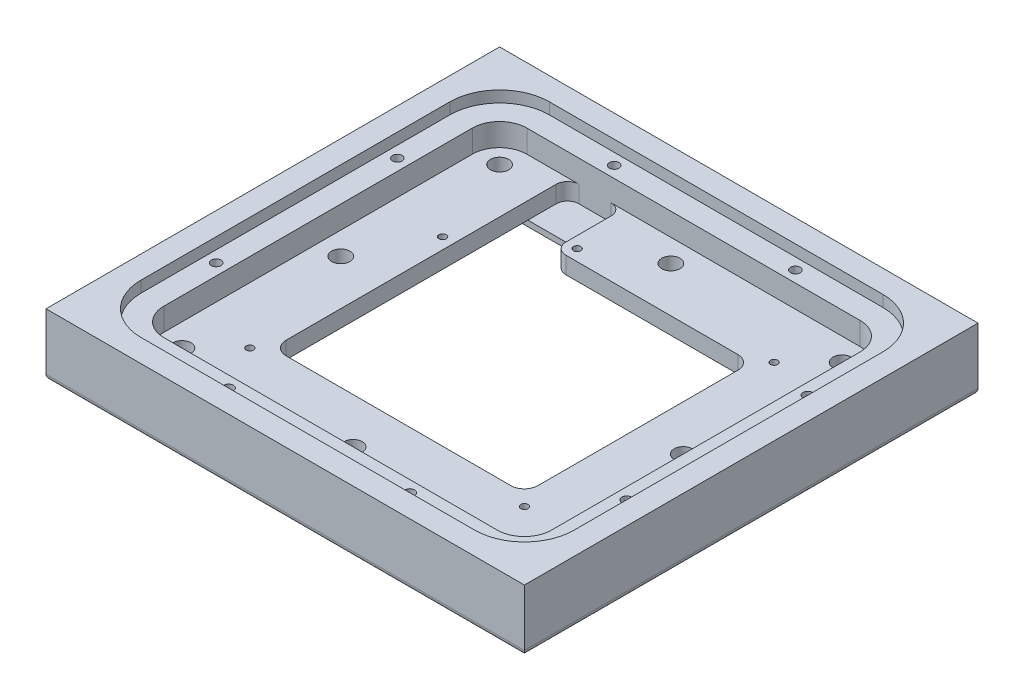
SolidWorks part; units mm, degrees
material "PE High Density"
ref_plane "Front Plane" through (0, 0, 0) normal (0, 0, 1) x (1, 0, 0)
ref_plane "Top Plane" through (0, 0, 0) normal (0, 1, 0) x (1, 0, 0)
ref_plane "Right Plane" through (0, 0, 0) normal (1, 0, 0) x (0, 0, -1)
sketch "Sketch2" plane through (0, 0, 0) normal (0, 1, 0) x (1, 0, 0)
  line L0 (-41.656, 22.1996) -> (-19.9136, 22.1996)
  line L1 (41.656, -38.1762) -> (-41.656, -38.1762)
  line L2 (41.656, -38.1762) -> (41.656, 38.1762)
  line L3 (41.656, 38.1762) -> (-41.656, 38.1762)
  line L4 (-41.656, -38.1762) -> (-41.656, 38.1762)
  line L5 (41.656, -38.1762) -> (-41.656, 38.1762) construction
  line L6 (41.656, 38.1762) -> (-41.656, -38.1762) construction
  line L7 (-19.9136, 22.1996) -> (-19.9136, 38.1762)
  line L8 (67.056, -63.5762) -> (-67.056, -63.5762)
  line L9 (-67.056, -63.5762) -> (-67.056, 63.5762)
  line L10 (67.056, 63.5762) -> (-67.056, 63.5762)
  line L11 (67.056, -63.5762) -> (67.056, 63.5762)
  point P0 (0, 0)
  point P13 (-38.481, -35.0012)
  point P14 (38.481, -35.0012)
  point P15 (38.481, 35.0012)
  point P16 (-16.7386, 35.0012)
  point P17 (-38.481, 19.0246)
  dimension "D1" = 83.312
  dimension "D2" = 76.3524
  dimension "D3" = 21.7424
  dimension "D4" = 15.9766
  dimension "D6" = 3.175
  dimension "D7" = 3.175
  dimension "D8" = 57.2008
  dimension "D9" = 80.137
  dimension "D10" = 24.9174
  dimension "D11" = 73.1774
  dimension "D5" = 25.4
extrude "Boss-Extrude1" add sketch "Sketch2" along normal blind 15.875 contours L8 L11 L10 L9 L1 L4 L3 L2 | L0 L7 L3 L4 region at (-30.7848, 0, -30.1879) region at (0, 0, 61.7281)
sketch "Sketch4" plane through (0, 0, 0) normal (0, 1, 0) x (1, 0, 0)
  line L0 (41.656, -38.1762) -> (41.656, 38.1762) construction
  line L1 (41.656, 38.1762) -> (-19.9136, 38.1762) construction
  line L2 (41.656, -38.1762) -> (-41.656, -38.1762) construction
  line L3 (-41.656, -38.1762) -> (-41.656, 22.1996) construction
  line L4 (-41.656, 22.1996) -> (-19.9136, 22.1996) construction
  line L5 (41.656, -38.1762) -> (41.656, 38.1762)
  line L6 (41.656, 38.1762) -> (-19.9136, 38.1762)
  line L7 (41.656, -38.1762) -> (-41.656, -38.1762)
  line L8 (-41.656, -38.1762) -> (-41.656, 22.1996)
  line L9 (-41.656, 22.1996) -> (-19.9136, 22.1996)
  line L10 (-19.9136, 22.1996) -> (-19.9136, 38.1762) construction
  line L11 (-19.9136, 22.1996) -> (-19.9136, 38.1762)
  line L12 (35.306, 31.8262) -> (-13.5636, 31.8262)
  line L13 (-13.5636, 15.8496) -> (-13.5636, 31.8262)
  line L14 (-35.306, 15.8496) -> (-13.5636, 15.8496)
  line L15 (-35.306, -31.8262) -> (-35.306, 15.8496)
  line L16 (35.306, -31.8262) -> (-35.306, -31.8262)
  line L17 (35.306, -31.8262) -> (35.306, 31.8262)
  dimension "D1" = 6.35
extrude "Boss-Extrude2" add sketch "Sketch4" along normal blind 9.525
sketch "Sketch5" plane through (0, 0, 0) normal (0, -1, 0) x (1, 0, 0)
  line L5 (46.736, -50.8762) -> (-46.736, -50.8762)
  line L6 (54.356, -43.2562) -> (54.356, 43.2562)
  line L7 (46.736, 50.8762) -> (-46.736, 50.8762)
  line L8 (-54.356, -43.2562) -> (-54.356, 43.2562)
  line L9 (54.356, -50.8762) -> (-54.356, 50.8762) construction
  line L10 (54.356, 50.8762) -> (-54.356, -50.8762) construction
  arc A0 (46.736, -50.8762) -> (54.356, -43.2562) centre (46.736, -43.2562) ccw
  arc A1 (-46.736, -50.8762) -> (-54.356, -43.2562) centre (-46.736, -43.2562) cw
  arc A2 (54.356, 43.2562) -> (46.736, 50.8762) centre (46.736, 43.2562) ccw
  arc A3 (-46.736, 50.8762) -> (-54.356, 43.2562) centre (-46.736, 43.2562) ccw
  point P0 (0, 0)
  dimension "D3" = 7.62
  dimension "D1" = 108.712
  dimension "D2" = 101.7524
extrude "Cut-Extrude2" cut sketch "Sketch5" against normal blind 3.175
hole_wizard "M2.5x0.45 Tapped Hole1" positions "Sketch6" profile "Sketch7" tap size "M2.5x0.45" standard "ANSI Metric"
sketch "Sketch6" plane through (0, 3.175, 0) normal (0, -1, 0) x (-1, 0, 0)
  point P0 (38.481, -35.0012)
  point P3 (-38.481, -35.0012)
  point P6 (38.481, 19.0246)
  point P9 (16.7386, 35.0012)
  point P12 (-38.481, 35.0012)
sketch "Sketch7" plane through (-38.481, 3.175, 35.0012) normal (1, 0, 0) x (0, 0, -1)
  line L0 (0, 0) -> (0, 6.9659)
  line L1 (0, 6.9659) -> (1.025, 6.35)
  line L2 (1.025, 6.35) -> (1.025, 0)
  line L5 (1.025, 0) -> (0, 0)
  line L10 (0, 6.9659) -> (-1.025, 6.35) construction
  line L11 (0, -6.35) -> (0, 107.95) construction
  dimension "Tap Drill Dia." = 2.05
  dimension "Tap Drill Depth" = 6.35
  dimension "Drill Angle" = 118
cosmetic thread "Hole Thread1" parameters "D1"=5.08, "D2"=2.5
cosmetic thread "Hole Thread2" parameters "D1"=5.08, "D2"=2.5
cosmetic thread "Hole Thread3" parameters "D1"=5.08, "D2"=2.5
cosmetic thread "Hole Thread4" parameters "D1"=5.08, "D2"=2.5
cosmetic thread "Hole Thread5" parameters "D1"=5.08, "D2"=2.5
hole_wizard "#10 Clearance Hole1" positions "Sketch8" profile "Sketch9" hole size "#10" standard "ANSI Inch" end condition through all
sketch "Sketch8" plane through (0, 3.175, 0) normal (0, -1, 0) x (-1, 0, 0)
  line L0 (54.356, -43.2562) -> (54.356, 43.2562) construction
  line L1 (-46.736, -50.8762) -> (46.736, -50.8762) construction
  line L2 (46.736, 50.8762) -> (-46.736, 50.8762) construction
  line L3 (-54.356, 43.2562) -> (-54.356, -43.2562) construction
  point P0 (48.006, -44.5262)
  point P2 (0, -44.5262)
  point P4 (-48.006, -44.5262)
  point P6 (-48.006, 0)
  point P8 (-48.006, 44.5262)
  point P10 (0, 44.5262)
  point P12 (48.006, 44.5262)
  point P14 (48.006, 0)
  dimension "D1" = 6.35
  dimension "D2" = 6.35
  dimension "D3" = 6.35
  dimension "D4" = 6.35
sketch "Sketch9" plane through (-48.006, 3.175, 44.5262) normal (1, 0, 0) x (0, 0, -1)
  line L0 (0, 0) -> (0, 12.7)
  line L1 (0, 12.7) -> (2.5527, 12.7)
  line L2 (2.5527, 12.7) -> (2.5527, 0)
  line L5 (2.5527, 0) -> (0, 0)
  line L11 (0, -6.35) -> (0, 107.95) construction
  dimension "Thru Hole Dia." = 5.1054
  dimension "Thru Hole Depth" = 12.7
sketch "Sketch10" plane through (0, 15.875, 0) normal (0, 1, 0) x (1, 0, 0)
  line L4 (54.356, -43.2562) -> (54.356, 43.2562)
  line L5 (-46.736, -50.8762) -> (46.736, -50.8762)
  line L6 (-54.356, 43.2562) -> (-54.356, -43.2562)
  line L7 (46.736, 50.8762) -> (-46.736, 50.8762)
  line L8 (54.356, -43.2562) -> (54.356, 43.2562)
  line L9 (-46.736, -50.8762) -> (46.736, -50.8762)
  line L10 (-54.356, 43.2562) -> (-54.356, -43.2562)
  line L11 (46.736, 50.8762) -> (-46.736, 50.8762)
  arc A4 (54.356, 43.2562) -> (46.736, 50.8762) centre (46.736, 43.2562) ccw
  arc A5 (46.736, -50.8762) -> (54.356, -43.2562) centre (46.736, -43.2562) ccw
  arc A6 (-54.356, -43.2562) -> (-46.736, -50.8762) centre (-46.736, -43.2562) ccw
  arc A7 (-46.736, 50.8762) -> (-54.356, 43.2562) centre (-46.736, 43.2562) ccw
  arc A8 (54.356, 43.2562) -> (46.736, 50.8762) centre (46.736, 43.2562) ccw
  arc A9 (46.736, -50.8762) -> (54.356, -43.2562) centre (46.736, -43.2562) ccw
  arc A10 (-54.356, -43.2562) -> (-46.736, -50.8762) centre (-46.736, -43.2562) ccw
  arc A11 (-46.736, 50.8762) -> (-54.356, 43.2562) centre (-46.736, 43.2562) ccw
  dimension "D1" = 0
extrude "Cut-Extrude3" cut sketch "Sketch10" against normal up to surface (6.35 mm away) up to face at (-38.481, 9.525, 33.9762)
sketch "Sketch11" plane through (0, 3.175, 0) normal (0, -1, 0) x (1, 0, 0)
  line L8 (43.2435, 39.7637) -> (-43.2435, 39.7637)
  line L9 (-43.2435, 39.7637) -> (-43.2435, -39.7637)
  line L10 (-43.2435, -39.7637) -> (43.2435, -39.7637)
  line L11 (43.2435, -39.7637) -> (43.2435, 39.7637)
  line L12 (40.0685, 39.7637) -> (-40.0685, 39.7637)
  line L13 (-43.2435, 36.5887) -> (-43.2435, -36.5887)
  line L14 (-40.0685, -39.7637) -> (40.0685, -39.7637)
  line L15 (43.2435, -36.5887) -> (43.2435, 36.5887)
  arc A0 (40.0685, -39.7637) -> (43.2435, -36.5887) centre (40.0685, -36.5887) ccw
  arc A1 (-43.2435, -36.5887) -> (-40.0685, -39.7637) centre (-40.0685, -36.5887) ccw
  arc A2 (40.0685, 39.7637) -> (43.2435, 36.5887) centre (40.0685, 36.5887) cw
  arc A3 (-40.0685, 39.7637) -> (-43.2435, 36.5887) centre (-40.0685, 36.5887) ccw
  dimension "D2" = 3.175
  dimension "D1" = 1.5875
extrude "Cut-Extrude4" cut sketch "Sketch11" against normal blind 1.6
sketch "Sketch12" plane through (0, 4.775, 0) normal (0, -1, 0) x (1, 0, 0)
  line L0 (-35.306, 31.8262) -> (-35.306, -15.8496) construction
  line L1 (35.306, 31.8262) -> (-35.306, 31.8262)
  line L2 (35.306, 31.8262) -> (35.306, -31.8262)
  line L3 (35.306, -31.8262) -> (-35.306, -31.8262)
  line L4 (-35.306, 31.8262) -> (-35.306, -31.8262)
  line L5 (-13.5636, -31.8262) -> (35.306, -31.8262) construction
extrude "Cut-Extrude5" cut sketch "Sketch12" against normal through all
fillet "Fillet1" radius 3.81 4 edges at (35.306, 7.15, -31.8262) (-35.306, 7.15, -31.8262) (35.306, 7.15, 31.8262) (-35.306, 7.15, 31.8262)
sketch "Sketch13" plane through (0, 0, 0) normal (0, -1, 0) x (1, 0, 0)
  line L4 (54.356, -43.2562) -> (54.356, 43.2562)
  line L5 (46.736, 50.8762) -> (-46.736, 50.8762)
  line L6 (-54.356, 43.2562) -> (-54.356, -43.2562)
  line L7 (-46.736, -50.8762) -> (46.736, -50.8762)
  line L8 (54.356, -43.2562) -> (54.356, 43.2562)
  line L9 (46.736, 50.8762) -> (-46.736, 50.8762)
  line L10 (-54.356, 43.2562) -> (-54.356, -43.2562)
  line L11 (-46.736, -50.8762) -> (46.736, -50.8762)
  line L12 (67.056, 63.5762) -> (-67.056, 63.5762)
  line L13 (-67.056, 63.5762) -> (-67.056, -63.5762)
  line L14 (-67.056, -63.5762) -> (67.056, -63.5762)
  line L15 (67.056, -63.5762) -> (67.056, 63.5762)
  line L16 (67.056, 63.5762) -> (-67.056, 63.5762)
  line L17 (-67.056, 63.5762) -> (-67.056, -63.5762)
  line L18 (-67.056, -63.5762) -> (67.056, -63.5762)
  line L19 (67.056, -63.5762) -> (67.056, 63.5762)
  arc A4 (46.736, -50.8762) -> (54.356, -43.2562) centre (46.736, -43.2562) ccw
  arc A5 (54.356, 43.2562) -> (46.736, 50.8762) centre (46.736, 43.2562) ccw
  arc A6 (-46.736, 50.8762) -> (-54.356, 43.2562) centre (-46.736, 43.2562) ccw
  arc A7 (-54.356, -43.2562) -> (-46.736, -50.8762) centre (-46.736, -43.2562) ccw
  arc A8 (46.736, -50.8762) -> (54.356, -43.2562) centre (46.736, -43.2562) ccw
  arc A9 (54.356, 43.2562) -> (46.736, 50.8762) centre (46.736, 43.2562) ccw
  arc A10 (-46.736, 50.8762) -> (-54.356, 43.2562) centre (-46.736, 43.2562) ccw
  arc A11 (-54.356, -43.2562) -> (-46.736, -50.8762) centre (-46.736, -43.2562) ccw
  dimension "D1" = 0
  dimension "D2" = 0
extrude "Cut-Extrude6" cut sketch "Sketch13" against normal blind 1.5875
fillet "Fillet2" radius 1.5875 4 edges at (67.056, 1.5875, 0) (0, 1.5875, 63.5762) (-67.056, 1.5875, 0) (0, 1.5875, -63.5762)
sketch "Sketch14" plane through (0, 9.525, 0) normal (0, 1, 0) x (1, 0, 0)
  line L1 (-35.306, 28.0162) -> (-19.9136, 28.0162)
  line L2 (-35.306, 28.0162) -> (-35.306, 50.8762)
  line L3 (-35.306, 50.8762) -> (-19.9136, 50.8762)
  line L4 (-19.9136, 28.0162) -> (-19.9136, 50.8762)
  line L6 (46.736, 50.8762) -> (-46.736, 50.8762) construction
  circle A0 centre (-16.7386, 35.0012) radius 1.025 construction
  dimension "D1" = 3.175
extrude "Cut-Extrude7" cut sketch "Sketch14" against normal up to surface (4.75 mm away) up to face at (0, 4.775, 0)
fillet "Fillet3" radius 3.175 3 edges at (-19.9136, 7.15, -50.8762) (-35.306, 7.15, -50.8762) (-19.9136, 7.15, -31.8262)
sketch "Sketch15" plane through (0, 15.875, 0) normal (0, 1, 0) x (1, 0, 0)
  line L0 (54.356, -43.2562) -> (54.356, 43.2562) construction
  line L1 (-46.736, -50.8762) -> (46.736, -50.8762) construction
  line L2 (-54.356, 43.2562) -> (-54.356, -43.2562) construction
  line L3 (46.736, 50.8762) -> (-46.736, 50.8762) construction
  line L4 (54.356, -43.2562) -> (54.356, 43.2562)
  line L5 (-46.736, -50.8762) -> (46.736, -50.8762)
  line L6 (-54.356, 43.2562) -> (-54.356, -43.2562)
  line L7 (46.736, 50.8762) -> (-46.736, 50.8762)
  line L8 (60.706, -43.2562) -> (60.706, 43.2562)
  line L9 (46.736, 57.2262) -> (-46.736, 57.2262)
  line L10 (-60.706, 43.2562) -> (-60.706, -43.2562)
  line L11 (-46.736, -57.2262) -> (46.736, -57.2262)
  line L16 (-67.056, -63.5762) -> (67.056, -63.5762)
  line L17 (67.056, -63.5762) -> (67.056, 63.5762)
  line L18 (67.056, 63.5762) -> (-67.056, 63.5762)
  line L19 (-67.056, 63.5762) -> (-67.056, -63.5762)
  line L20 (-67.056, -63.5762) -> (67.056, -63.5762)
  line L21 (67.056, -63.5762) -> (67.056, 63.5762)
  line L22 (67.056, 63.5762) -> (-67.056, 63.5762)
  line L23 (-67.056, 63.5762) -> (-67.056, -63.5762)
  arc A0 (46.736, -50.8762) -> (54.356, -43.2562) centre (46.736, -43.2562) ccw construction
  arc A1 (-54.356, -43.2562) -> (-46.736, -50.8762) centre (-46.736, -43.2562) ccw construction
  arc A2 (54.356, 43.2562) -> (46.736, 50.8762) centre (46.736, 43.2562) ccw construction
  arc A3 (-46.736, 50.8762) -> (-54.356, 43.2562) centre (-46.736, 43.2562) ccw construction
  arc A4 (46.736, -50.8762) -> (54.356, -43.2562) centre (46.736, -43.2562) ccw
  arc A5 (-54.356, -43.2562) -> (-46.736, -50.8762) centre (-46.736, -43.2562) ccw
  arc A6 (54.356, 43.2562) -> (46.736, 50.8762) centre (46.736, 43.2562) ccw
  arc A7 (-46.736, 50.8762) -> (-54.356, 43.2562) centre (-46.736, 43.2562) ccw
  arc A8 (60.706, 43.2562) -> (46.736, 57.2262) centre (46.736, 43.2562) ccw
  arc A9 (-46.736, 57.2262) -> (-60.706, 43.2562) centre (-46.736, 43.2562) ccw
  arc A10 (-60.706, -43.2562) -> (-46.736, -57.2262) centre (-46.736, -43.2562) ccw
  arc A11 (46.736, -57.2262) -> (60.706, -43.2562) centre (46.736, -43.2562) ccw
  line M29 (-67.056, -63.5762) -> (67.056, -63.5762)
  line M30 (67.056, -63.5762) -> (67.056, 63.5762)
  line M31 (67.056, 63.5762) -> (-67.056, 63.5762)
  line M32 (-67.056, 63.5762) -> (-67.056, -63.5762)
  dimension "D1" = 6.35
  dimension "D2" = 0
extrude "Boss-Extrude3" add sketch "Sketch15" along normal blind 3.175 contours A11 L11 A10 L10 A9 L9 A8 L8 M32 M29 M30 M31 region at (-65.2079, 15.875, 0)
hole_wizard "#6-32 Tapped Hole1" positions "Sketch16" profile "Sketch18" tap size "#6-32" standard "ANSI Inch"
sketch "Sketch16" plane through (0, 15.875, 0) normal (0, 1, 0) x (1, 0, 0)
  line L28 (57.531, -43.2562) -> (57.531, 43.2562)
  line L29 (-46.736, -54.0512) -> (46.736, -54.0512)
  line L30 (-57.531, 43.2562) -> (-57.531, -43.2562)
  line L31 (46.736, 54.0512) -> (-46.736, 54.0512)
  line L32 (57.531, -43.2562) -> (57.531, 43.2562) construction
  line L33 (-46.736, -54.0512) -> (46.736, -54.0512) construction
  line L34 (-57.531, 43.2562) -> (-57.531, -43.2562) construction
  line L35 (46.736, 54.0512) -> (-46.736, 54.0512) construction
  arc A24 (57.531, 43.2562) -> (46.736, 54.0512) centre (46.736, 43.2562) ccw
  arc A25 (46.736, -54.0512) -> (57.531, -43.2562) centre (46.736, -43.2562) ccw
  arc A26 (-57.531, -43.2562) -> (-46.736, -54.0512) centre (-46.736, -43.2562) ccw
  arc A27 (-46.736, 54.0512) -> (-57.531, 43.2562) centre (-46.736, 43.2562) ccw
  arc A28 (57.531, 43.2562) -> (46.736, 54.0512) centre (46.736, 43.2562) ccw construction
  arc A29 (46.736, -54.0512) -> (57.531, -43.2562) centre (46.736, -43.2562) ccw construction
  arc A30 (-57.531, -43.2562) -> (-46.736, -54.0512) centre (-46.736, -43.2562) ccw construction
  arc A31 (-46.736, 54.0512) -> (-57.531, 43.2562) centre (-46.736, 43.2562) ccw construction
  point P141 (-25.4, 54.0512)
  point P143 (-57.531, 25.4)
  point P145 (-57.531, -25.4)
  point P147 (-25.4, -54.0512)
  dimension "D2" = 25.4
  dimension "D3" = 25.4
  dimension "D4" = 25.4
  dimension "D1" = 3.175
cosmetic thread "Hole Thread6" parameters "D1"=14.224, "D2"=3.5052
cosmetic thread "Hole Thread7" parameters "D1"=14.224, "D2"=3.5052
cosmetic thread "Hole Thread8" parameters "D1"=14.224, "D2"=3.5052
cosmetic thread "Hole Thread9" parameters "D1"=14.224, "D2"=3.5052
sketch "Sketch18" plane through (-25.4, 15.875, 54.0512) normal (1, 0, 0) x (0, 0, 1)
  line L0 (0, 0) -> (0, 10.3377)
  line L1 (0, 10.3377) -> (1.3525, 9.525)
  line L2 (1.3525, 9.525) -> (1.3525, 0)
  line L5 (1.3525, 0) -> (0, 0)
  line L10 (0, 10.3377) -> (-1.3526, 9.525) construction
  line L11 (0, -6.35) -> (0, 107.95) construction
  dimension "Tap Drill Dia." = 2.7051
  dimension "Tap Drill Depth" = 9.525
  dimension "Drill Angle" = 118
mirror "Mirror1" about plane through (0, 0, 0) normal (1, 0, 0) of "#6-32 Tapped Hole1"
cosmetic thread "Hole Thread10" parameters "D1"=14.224, "D2"=3.5052
cosmetic thread "Hole Thread11" parameters "D1"=14.224, "D2"=3.5052
cosmetic thread "Hole Thread12" parameters "D1"=14.224, "D2"=3.5052
cosmetic thread "Hole Thread13" parameters "D1"=14.224, "D2"=3.5052
equation "\"D3@Sketch16\"=\"D2@Sketch16\""
equation "\"D4@Sketch16\"=\"D2@Sketch16\""
